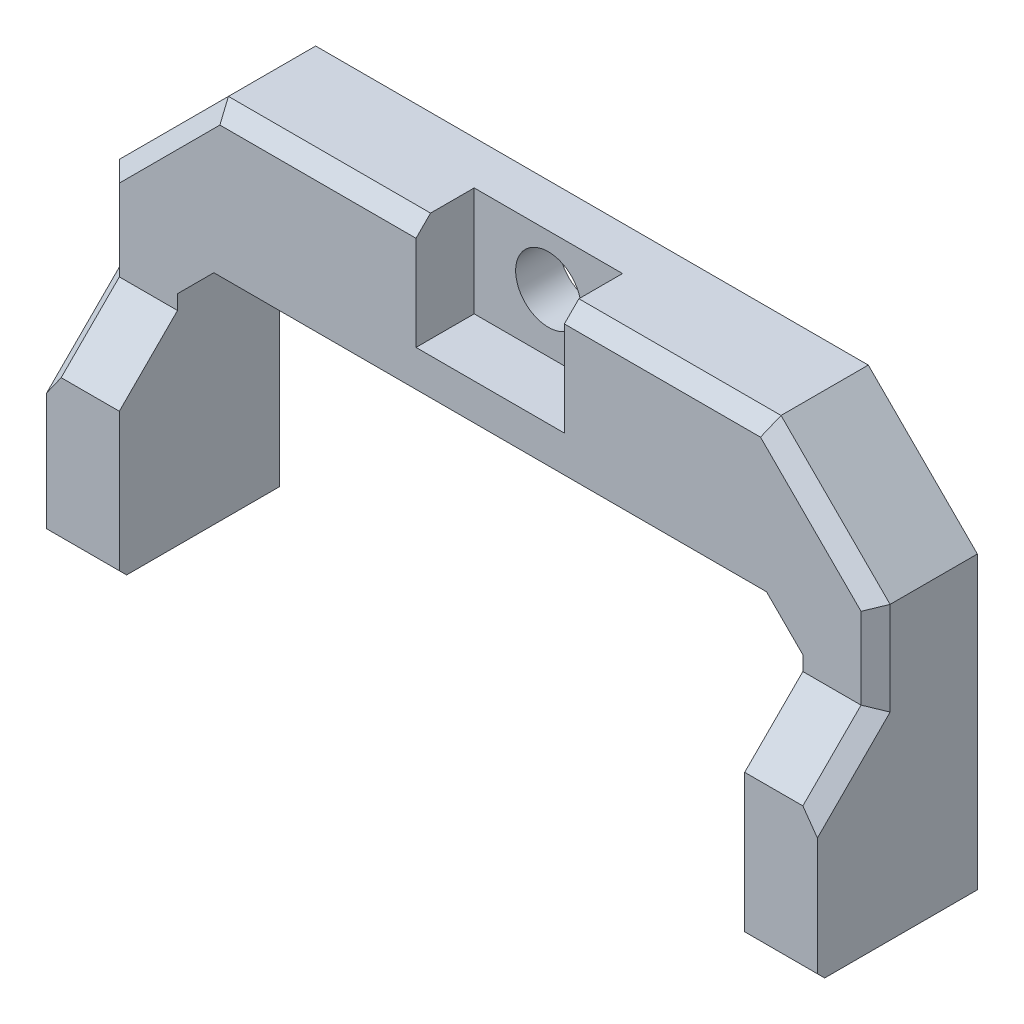
SolidWorks part; units mm, degrees
ref_plane "Front Plane" through (0, 0, 0) normal (0, 0, 1) x (1, 0, 0)
ref_plane "Top Plane" through (0, 0, 0) normal (0, 1, 0) x (1, 0, 0)
ref_plane "Right Plane" through (0, 0, 0) normal (1, 0, 0) x (0, 0, -1)
sketch "Sketch1" plane through (0, 0, 0) normal (0, 0, 1) x (1, 0, 0)
  line L0 (0, 0) -> (0, -10)
  line L1 (0, -10) -> (-19, -10)
  line L2 (-19, -10) -> (-21.5, -12.5)
  line L3 (-21.5, -12.5) -> (-21.5, -27.5)
  line L4 (-21.5, -27.5) -> (-26.5, -27.5)
  line L5 (-26.5, -27.5) -> (-26.5, -7.5)
  line L6 (-26.5, -7.5) -> (-19, 0)
  line L7 (-19, 0) -> (0, 0)
  dimension "D1" = 135
  dimension "D2" = 21.5
  dimension "D3" = 5
  dimension "D4" = 15
  dimension "D5" = 10
  dimension "D6" = 2.5
extrude "Boss-Extrude1" add sketch "Sketch1" along normal blind 7
sketch "Sketch6" plane through (0, 0, 7) normal (0, 0, 1) x (1, 0, 0)
  line L0 (-21.5, -27.5) -> (-21.5, -12.5) construction
  line L1 (-26.5, -27.5) -> (-21.5, -27.5)
  line L2 (-26.5, -27.5) -> (-26.5, -17.5)
  line L3 (-26.5, -17.5) -> (-21.5, -17.5)
  line L4 (-21.5, -27.5) -> (-21.5, -17.5)
  dimension "D1" = 10
extrude "Boss-Extrude2" add sketch "Sketch6" along normal blind 4
sketch "Sketch3" plane through (0, 0, 7) normal (0, 0, 1) x (1, 0, 0)
  line L1 (0, 0) -> (-5.1, 0)
  line L2 (0, 0) -> (0, -7.5)
  line L3 (0, -7.5) -> (-5.1, -7.5)
  line L4 (-5.1, 0) -> (-5.1, -7.5)
  dimension "D1" = 7.5
  dimension "D2" = 5.1
extrude "Cut-Extrude1" cut sketch "Sketch3" against normal blind 4
mirror "Mirror1" about plane through (0, 0, 7) normal (-1, 0, 0) of "Boss-Extrude2", "Boss-Extrude1", "Cut-Extrude1"
hole_wizard "M4 Clearance Hole1" positions "Sketch4" profile "Sketch5" hole size "M4" standard "ANSI Metric" end condition through all
sketch "Sketch4" plane through (0, 0, 3) normal (0, 0, 1) x (1, 0, 0)
  line L0 (-5.1, -7.5) -> (5.1, -7.5) construction
  line L1 (0, -3.85) -> (0, 3.85) construction
  point P0 (0, -3.5)
  dimension "D1" = 4
sketch "Sketch5" plane through (0, -3.5, 3) normal (1, 0, 0) x (0, -1, 0)
  line L0 (0, 0) -> (0, 3)
  line L1 (0, 3) -> (2.25, 3)
  line L2 (2.25, 3) -> (2.25, 0)
  line L5 (2.25, 0) -> (0, 0)
  line L11 (0, -6.35) -> (0, 107.95) construction
  dimension "Thru Hole Dia." = 4.5
  dimension "Thru Hole Depth" = 3
chamfer "Chamfer2" distance 4 2 edges at (24, -17.5, 7) (-24, -17.5, 7)
chamfer "Chamfer3" distance 0.5 distance2 0.5 2 edges at (24, -27.5, 11) (-24, -27.5, 11)
chamfer "Chamfer4" distance 1 angle 45 8 edges at (26.5, -10.5, 7) (22.75, -3.75, 7) (12.05, 0, 7) (-26.5, -10.5, 7) (-22.75, -3.75, 7) (-12.05, 0, 7) (26.5, -15.5, 9) (-26.5, -15.5, 9)
equation "\"a\"=1"
